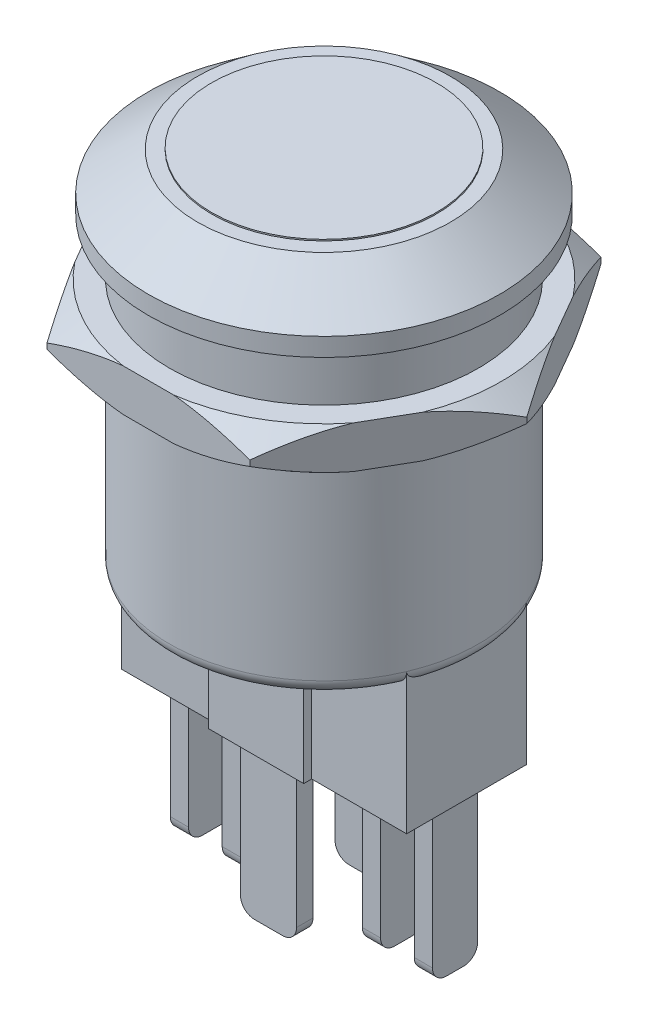
SolidWorks part; units mm, degrees
ref_plane "前视基准面" through (0, 0, 0) normal (0, 0, 1) x (1, 0, 0)
ref_plane "上视基准面" through (0, 0, 0) normal (0, 1, 0) x (1, 0, 0)
ref_plane "右视基准面" through (0, 0, 0) normal (1, 0, 0) x (0, 0, -1)
sketch "草图1" plane through (0, 0, 0) normal (0, 1, 0) x (1, 0, 0)
  circle A0 centre (0, 0) radius 11
  dimension "D1" = 22
extrude "凸台-拉伸1" add sketch "草图1" along normal blind 15
sketch "草图8" plane through (0, 0, 0) normal (0, -1, 0) x (1, 0, 0)
  line L0 (-3.3825, 4.2596) -> (-3.3825, 4.8256)
  line L1 (10.1418, -4.2596) -> (3.3825, -4.2596)
  line L2 (10.1418, -4.2596) -> (10.1418, 4.2596)
  line L3 (10.1418, 4.2596) -> (3.3825, 4.2596)
  line L4 (-10.1418, -4.2596) -> (-10.1418, 4.2596)
  line L5 (10.1418, -4.2596) -> (-10.1418, 4.2596) construction
  line L6 (10.1418, 4.2596) -> (-10.1418, -4.2596) construction
  line L7 (-3.3825, -4.8256) -> (3.3825, -4.8256)
  line L8 (-3.3825, -4.8256) -> (-3.3825, -4.2596)
  line L9 (-3.3825, 4.8256) -> (3.3825, 4.8256)
  line L10 (3.3825, -4.8256) -> (3.3825, -4.2596)
  line L11 (-3.3825, -4.8256) -> (3.3825, 4.8256) construction
  line L12 (-3.3825, 4.8256) -> (3.3825, -4.8256) construction
  line L13 (-3.3825, -4.2596) -> (-10.1418, -4.2596)
  line L14 (-3.3825, 4.2596) -> (-10.1418, 4.2596)
  line L15 (3.3825, 4.2596) -> (3.3825, 4.8256)
  circle A0 centre (0, 0) radius 11 construction
  point P0 (0, 0)
  point P8 (0, 0)
extrude "凸台-拉伸5" add sketch "草图8" along normal blind 9
sketch "草图2" plane through (0, 0, 0) normal (0, -1, 0) x (1, 0, 0)
  line L0 (0, 0) -> (0, 7.9124) construction
  line L1 (3.6947, 0) -> (-4.9885, 0) construction
  line L2 (-5.6352, 1.6103) -> (-4.3417, 1.6103)
  line L3 (-4.3417, -1.6103) -> (-4.3417, 1.6103)
  line L4 (-5.6352, -1.6103) -> (-5.6352, 1.6103)
  line L5 (-5.6352, -1.6103) -> (-4.3417, -1.6103)
  line L6 (5.6352, -1.6103) -> (4.3417, -1.6103)
  line L7 (0, 0) -> (-8.6832, 0) construction
  line L8 (9.33, 1.6103) -> (8.0364, -1.6103) construction
  line L9 (9.33, -1.6103) -> (8.0364, 1.6103) construction
  line L10 (5.6352, 1.6103) -> (4.3417, 1.6103)
  line L11 (4.3417, -1.6103) -> (4.3417, 1.6103)
  line L12 (8.0364, -1.6103) -> (8.0364, 1.6103)
  line L13 (-9.33, -1.6103) -> (-8.0364, -1.6103)
  line L14 (-9.33, -1.6103) -> (-9.33, 1.6103)
  line L15 (-9.33, 1.6103) -> (-8.0364, 1.6103)
  line L16 (-8.0364, -1.6103) -> (-8.0364, 1.6103)
  line L17 (-9.33, -1.6103) -> (-8.0364, 1.6103) construction
  line L18 (-9.33, 1.6103) -> (-8.0364, -1.6103) construction
  line L19 (9.33, 1.6103) -> (8.0364, 1.6103)
  line L20 (9.33, -1.6103) -> (9.33, 1.6103)
  line L21 (9.33, -1.6103) -> (8.0364, -1.6103)
  line L22 (5.6352, -1.6103) -> (5.6352, 1.6103)
  line L23 (1.9974, -2.7841) -> (1.9974, -3.9524)
  line L24 (1.9974, 2.7841) -> (-1.9974, 2.7841)
  line L25 (1.9974, 2.7841) -> (1.9974, 3.9524)
  line L26 (1.9974, 3.9524) -> (-1.9974, 3.9524)
  line L27 (-1.9974, 2.7841) -> (-1.9974, 3.9524)
  line L28 (1.9974, 2.7841) -> (-1.9974, 3.9524) construction
  line L29 (1.9974, 3.9524) -> (-1.9974, 2.7841) construction
  line L30 (1.9974, -2.7841) -> (-1.9974, -2.7841)
  line L31 (1.9974, -3.9524) -> (-1.9974, -3.9524)
  line L32 (-1.9974, -2.7841) -> (-1.9974, -3.9524)
  point P0 (0, 3.3682)
  point P10 (-8.6832, 0)
  point P23 (8.6832, 0)
  dimension "D1" = 2
extrude "凸台-拉伸2" add sketch "草图2" along normal blind 11 from surface at 9 starting at face at (0, -9, 0)
sketch "草图9" plane through (0, 15, 0) normal (0, 1, 0) x (1, 0, 0)
  line L1 (-7.2169, 12.5) -> (-14.4338, 0)
  line L2 (-14.4338, 0) -> (-7.2169, -12.5)
  line L3 (-7.2169, -12.5) -> (7.2169, -12.5)
  line L4 (7.2169, -12.5) -> (14.4338, 0)
  line L5 (14.4338, 0) -> (7.2169, 12.5)
  line L6 (7.2169, 12.5) -> (-7.2169, 12.5)
  circle A0 centre (0, 0) radius 12.5 construction
  circle A1 centre (0, 0) radius 12.5 construction
  dimension "D1" = 25
extrude "凸台-拉伸6" add sketch "草图9" along normal blind 3
sketch "草图10" plane through (0, 18, 0) normal (0, 1, 0) x (1, 0, 0)
  circle A0 centre (0, 0) radius 12.5
  dimension "D1" = 25
extrude "凸台-拉伸7" add sketch "草图10" along normal blind 8
chamfer "倒角2" distance 2.7 distance2 3.5 1 edges at (0, 26, 12.5) first distance on face at (0, 26, 12.5)
sketch "草图12" plane through (0, 0, 0) normal (0, 0, 1) x (1, 0, 0)
  line L0 (-12.6295, 18) -> (-14.4338, 16.7)
  line L1 (-14.4338, 18) -> (-10.8253, 18) construction
  line L2 (-14.4338, 18) -> (-14.4338, 15) construction
  line L3 (-14.4338, 16.5) -> (-11.8121, 16.5) construction
  line L4 (-12.6295, 15) -> (-14.4338, 16.3)
  line L5 (-12.6295, 18) -> (-12.6295, 18.5)
  line L6 (-12.6295, 18.5) -> (-14.9338, 18.5)
  line L7 (-14.9338, 18.5) -> (-14.9338, 14.5)
  line L8 (-14.9338, 14.5) -> (-12.6295, 14.5)
  line L9 (-12.6295, 14.5) -> (-12.6295, 15)
  line L10 (-14.4338, 16.7) -> (-14.4338, 16.3)
  line L11 (0, 15) -> (0, 29.2248) construction
  line L12 (-11, 15) -> (11, 15) construction
  dimension "D1" = 1.3
  dimension "D2" = 0.5
  dimension "D3" = 0.5
  dimension "D4" = 0.5
revolve "切除-旋转1" cut sketch "草图12" angle 360 about L11
fillet "圆角2" radius 1 2 edges at (0, 0, -11) (0, 0, 11)
fillet "圆角3" radius 1 2 edges at (11, 0, 0) (-11, 0, 0)
sketch "草图13" plane through (0, 26, 0) normal (0, 1, 0) x (1, 0, 0)
  circle A0 centre (0, 0) radius 8
  dimension "D1" = 16
extrude "凸台-拉伸8" add sketch "草图13" along normal blind 0.1
fillet "圆角5" radius 1 12 edges at (-8.6832, -20, -1.6103) (-8.6832, -20, 1.6103) (-4.9885, -20, -1.6103) (-4.9885, -20, 1.6103) (1.9974, -20, 3.3682) (-1.9974, -20, 3.3682) (-1.9974, -20, -3.3682) (1.9974, -20, -3.3682) (4.9885, -20, -1.6103) (4.9885, -20, 1.6103) (8.6832, -20, -1.6103) (8.6832, -20, 1.6103)
sketch "草图15" plane through (0, 18, 0) normal (0, 1, 0) x (1, 0, 0)
  circle A1 centre (0, 0) radius 12.5
  circle A2 centre (0, 0) radius 11
  circle A3 centre (0, 0) radius 11 construction
  circle A4 centre (0, 0) radius 12.5 construction
extrude "切除-拉伸4" cut sketch "草图15" along normal blind 4
